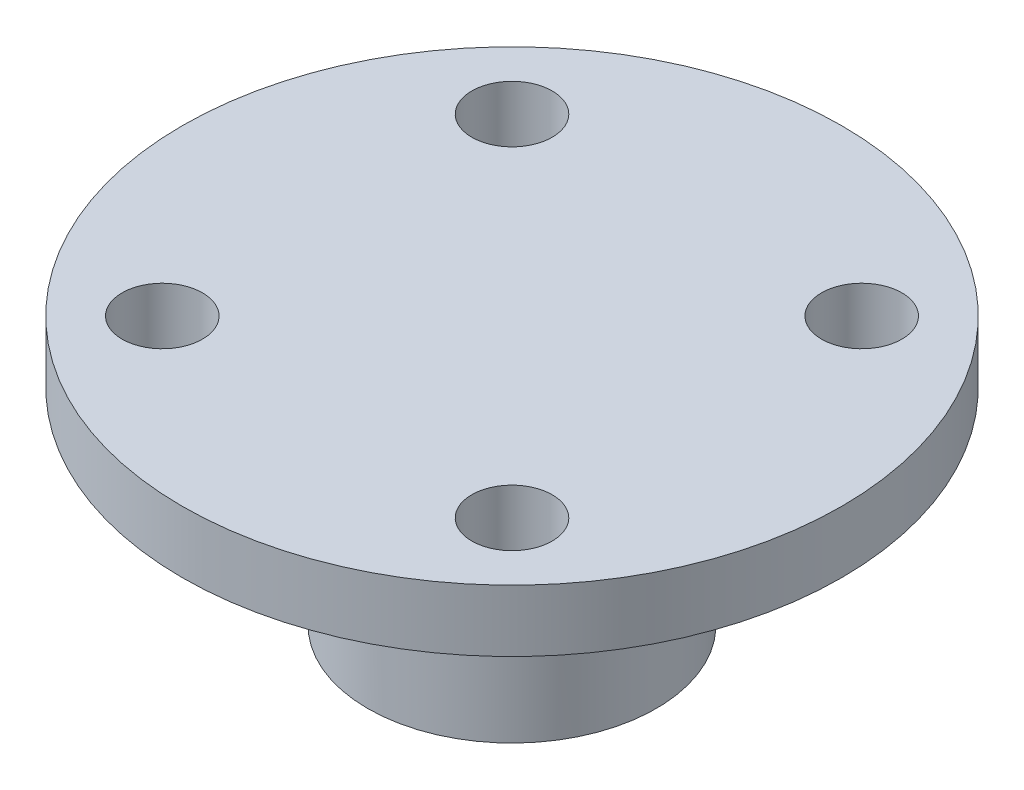
SolidWorks part; units mm, degrees
ref_plane "Front Plane" through (0, 0, 0) normal (0, 0, 1) x (1, 0, 0)
ref_plane "Top Plane" through (0, 0, 0) normal (0, 1, 0) x (1, 0, 0)
ref_plane "Right Plane" through (0, 0, 0) normal (1, 0, 0) x (0, 0, -1)
sketch "Sketch1" plane through (0, 0, 0) normal (0, 1, 0) x (1, 0, 0)
  line L1 (-16, -16) -> (16, -16)
  line L2 (-16, -16) -> (-16, 16)
  line L3 (-16, 16) -> (16, 16)
  line L4 (16, -16) -> (16, 16)
  line L5 (-16, -16) -> (16, 16) construction
  line L6 (-16, 16) -> (16, -16) construction
  circle A0 centre (0, 0) radius 16
  circle A1 centre (0, 0) radius 8
  dimension "D1" = 32
  dimension "D2" = 16
extrude "Boss-Extrude1" add sketch "Sketch1" along normal blind 3 contours A0 A1 | A1 region at (-10.9937, 0, 10.9937)
sketch "Sketch2" plane through (0, 3, 0) normal (0, 1, 0) x (1, 0, 0)
  line L1 (-16, -16) -> (16, -16)
  line L2 (-16, -16) -> (-16, 16)
  line L3 (-16, 16) -> (16, 16)
  line L4 (16, -16) -> (16, 16)
  line L5 (-16, -16) -> (16, 16) construction
  line L6 (-16, 16) -> (16, -16) construction
  line L7 (-5.8336, 11.1369) -> (-11.1369, 5.8336) construction
  circle A0 centre (0, 0) radius 16 construction
  point P0 (0, 0)
  point P15 (-8.4853, 8.4853)
  point P18 (8.4853, 8.4853)
  point P19 (8.4853, -8.4853)
  point P20 (-8.4853, -8.4853)
  dimension "D2" = 12
  dimension "D3" = 7.5
  dimension "D5" = 12
  dimension "D4" = 4
sketch "Sketch6" plane through (0, 0, 0) normal (0, -1, 0) x (1, 0, 0)
  line L0 (2.6458, 3) -> (-2.6458, 3)
  circle A1 centre (0, 0) radius 4
  circle A3 centre (0, 0) radius 7
  dimension "D2" = 8
  dimension "D1" = 3
  dimension "D3" = 3
extrude "Boss-Extrude2" add sketch "Sketch6" along normal blind 10 contours L0 | A3 region at (0, 0, 3.4046) region at (-6.802, 0, 0)
ref_plane "Plane1" through (0, 0, 7) normal (0, 0, 1) x (1, 0, 0)
sketch "Sketch7" plane through (0, 0, 0) normal (0, 0, 1) x (1, 0, 0)
  circle A0 centre (0, -5) radius 1
  circle A1 centre (0, -5) radius 1.9
  point P10 (0, -5)
  dimension "D1" = 2
  dimension "D2" = 3.8
  dimension "D3" = 5
extrude "Cut-Extrude1" cut sketch "Sketch7" along normal blind 10.5 contours A0
sketch "Sketch11" plane through (0, 0, 7) normal (0, 0, 1) x (1, 0, 0)
  line L0 (0, 0) -> (0, -6.35)
  circle A0 centre (0, -5) radius 1.9
  dimension "D1" = 3.8
  dimension "D2" = 6.35
extrude "Cut-Extrude2" cut sketch "Sketch11" against normal blind 2 contours A0 region at (-1.3055, -6.3055, 7)
hole_wizard "Ø3.0mm Dowel Hole1" positions "3DSketch1" profile "Sketch12" hole size "Ø3.0" standard "ANSI Metric" end condition through all
sketch3d "3DSketch1"
  point P0 (8.4853, 3, 8.4853)
  point P3 (-8.4853, 3, 8.4853)
  point P6 (-8.4853, 3, -8.4853)
  point P9 (8.4853, 3, -8.4853)
sketch "Sketch12" plane through (8.4853, 3, 8.4853) normal (1, 0, 0) x (0, 0, 1)
  line L0 (0, 0) -> (0, 13)
  line L1 (0, 13) -> (1.95, 13)
  line L2 (1.95, 13) -> (1.95, 0)
  line L5 (1.95, 0) -> (0, 0)
  line L11 (0, -6.35) -> (0, 107.95) construction
  dimension "Thru Hole Dia." = 3.9
  dimension "Thru Hole Depth" = 13
